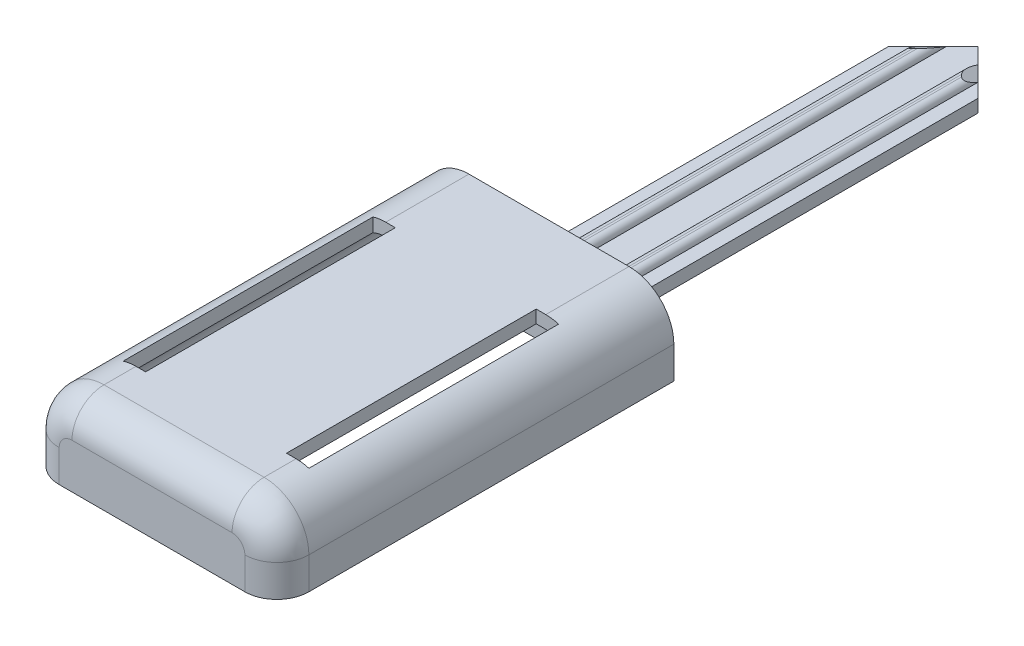
SolidWorks part; units mm, degrees
note: The reader was unsure of these and kept them because the rebuilt part matched: shared geometry of "Sketch2<2>".
ref_plane "Front" through (0, 0, 0) normal (0, 0, 1) x (1, 0, 0)
ref_plane "Top" through (0, 0, 0) normal (0, 1, 0) x (1, 0, 0)
ref_plane "Right" through (0, 0, 0) normal (1, 0, 0) x (0, 0, -1)
sketch "Sketch1" plane through (0, 0, 0) normal (0, 0, 1) x (1, 0, 0)
  line L0 (-12.5, 0) -> (12.5, 0)
  line L1 (-17.5, -5) -> (-17.5, -10)
  line L2 (17.5, -5) -> (17.5, -10)
  line L3 (-19.5, -5) -> (-19.5, -10)
  line L4 (-12.5, 2) -> (12.5, 2)
  line L5 (19.5, -5) -> (19.5, -10)
  line L6 (19.5, -10) -> (17.5, -10)
  line L7 (-17.5, -10) -> (-19.5, -10)
  line L8 (19.5, -10) -> (-49980.5, -10) construction
  arc A0 (12.5, 0) -> (17.5, -5) centre (12.5, -5) cw
  arc A1 (-12.5, 0) -> (-17.5, -5) centre (-12.5, -5) ccw
  arc A2 (-12.5, 2) -> (-19.5, -5) centre (-12.5, -5) ccw
  arc A3 (12.5, 2) -> (19.5, -5) centre (12.5, -5) cw
  point P4 (0, 0)
  point P8 (17.5, 0)
  point P11 (-17.5, 0)
  dimension "D2" = 5
  dimension "D1" = 35
  dimension "D4" = 12
  dimension "D3" = 2
extrude "Boss-Extrude1" add sketch "Sketch1" along normal blind 60
sketch "Sketch2" plane through (0, 0, 0) normal (0, 0, 1) x (1, 0, 0)
  line L0 (19.5, -10) -> (19.5, -5) construction
  line L1 (12.5, 2) -> (-12.5, 2) construction
  line L2 (-19.5, -5) -> (-19.5, -10) construction
  line L3 (19.5, -10) -> (19.5, -5)
  line L4 (12.5, 2) -> (-12.5, 2)
  line L5 (-19.5, -5) -> (-19.5, -10)
  line L6 (-19.5, -10) -> (19.5, -10)
  arc A0 (19.5, -5) -> (12.5, 2) centre (12.5, -5) ccw construction
  arc A1 (-12.5, 2) -> (-19.5, -5) centre (-12.5, -5) ccw construction
  arc A2 (19.5, -5) -> (12.5, 2) centre (12.5, -5) ccw
  arc A3 (-12.5, 2) -> (-19.5, -5) centre (-12.5, -5) ccw
extrude "Boss-Extrude2" add sketch "Sketch2" along normal blind 2
extrude "Boss-Extrude3" add sketch "Sketch2<2>" along normal blind 2 from surface at 60 starting at face at (0, -4.2525, 60)
sketch "Sketch2<2>" plane through (0, 0, 0) normal (0, 0, 1) x (1, 0, 0) same geometry as "Sketch2"
fillet "Fillet1" radius 5 10 edges at (19.5, -7.5, 62) (17.4497, -0.0503, 62) (-19.5, -7.5, 62) (-17.4497, -0.0503, 62) (0, 2, 62) (-17.5, -7.5, 60) (17.5, -7.5, 60) (16.0355, -1.4645, 60) (0, 0, 60) (-16.0355, -1.4645, 60)
sketch "Sketch3" plane through (0, -10, 0) normal (0, -1, 0) x (1, 0, 0)
  line L0 (0, 0) -> (0, -50000) construction
  line L1 (-19.5, 0) -> (19.5, 0) construction
  line L2 (-7, 0) -> (-7, -60)
  line L3 (-7, -60) -> (0, -67)
  line L4 (-7, 0) -> (7, 0)
  line L5 (7, -60) -> (0, -67)
  line L6 (7, 0) -> (7, -60)
  point P4 (0, 0)
  point P11 (0, 0)
  dimension "D1" = 7
  dimension "D2" = 45
  dimension "D3" = 60
extrude "Boss-Extrude4" add sketch "Sketch3" against normal blind 2
fillet "Fillet2" radius 2 3 edges at (7, -9, 0) (-7, -9, 0) (0, -8, 0)
sketch "Sketch4" plane through (0, -10, 0) normal (0, -1, 0) x (1, 0, 0)
  line L0 (-17.5, 2) -> (17.5, 2) construction
  line L1 (17.5, 55) -> (17.5, 2) construction
  line L2 (-17.5, 55) -> (-17.5, 2) construction
  line L3 (-12.5, 60) -> (12.5, 60) construction
  line L4 (-17.5, 2) -> (17.5, 2)
  line L5 (17.5, 55) -> (17.5, 2)
  line L6 (-17.5, 55) -> (-17.5, 2)
  line L7 (-12.5, 60) -> (12.5, 60)
  line L8 (-16.5, 3) -> (16.5, 3)
  line L9 (16.5, 55) -> (16.5, 3)
  line L10 (-12.5, 59) -> (12.5, 59)
  line L11 (-16.5, 55) -> (-16.5, 3)
  arc A0 (17.5, 55) -> (12.5, 60) centre (12.5, 55) ccw construction
  arc A1 (-12.5, 60) -> (-17.5, 55) centre (-12.5, 55) ccw construction
  arc A2 (17.5, 55) -> (12.5, 60) centre (12.5, 55) ccw
  arc A3 (-12.5, 60) -> (-17.5, 55) centre (-12.5, 55) ccw
  arc A4 (16.5, 55) -> (12.5, 59) centre (12.5, 55) ccw
  arc A5 (-12.5, 59) -> (-16.5, 55) centre (-12.5, 55) ccw
  dimension "D1" = 1
extrude "Boss-Extrude5" add sketch "Sketch4" along normal blind 2 and the other way blind 1
chamfer "Chamfer3" distance 1 angle 45 6 edges at (17.5, -9, 28.5) (16.0355, -9, 58.5355) (0, -9, 60) (-16.0355, -9, 58.5355) (0, -9, 2) (-17.5, -9, 28.5)
sketch "Sketch5" plane through (0, -8, 0) normal (0, 1, 0) x (1, 0, 0)
  line L0 (0, 0) -> (0, 50000) construction
  line L1 (0, 0) -> (-50000, 0) construction
  line L2 (-7, 60) -> (0, 67) construction
  line L3 (-4.826, 0) -> (-2.4776, 0)
  line L4 (-4.826, 0) -> (-4.826, 62.174)
  line L6 (-2.4776, 0) -> (-2.4776, 64.5224)
  line L7 (-2.4776, 64.5224) -> (-4.826, 62.174)
  line L8 (4.826, 0) -> (4.826, 62.174)
  line L9 (2.4776, 64.5224) -> (4.826, 62.174)
  line L10 (2.4776, 0) -> (2.4776, 64.5224)
  line L11 (4.826, 0) -> (2.4776, 0)
extrude "Boss-Extrude6" add sketch "Sketch5" along normal blind 1
fillet "Fillet3" radius 1 4 edges at (4.826, -7, -31.221) (2.4776, -7, -32.3952) (-2.4776, -7, -32.3952) (-4.826, -7, -31.221)
chamfer "Chamfer4" distance 1 angle 61 2 edges at (-3.6518, -7, -63.3482) (3.6518, -7, -63.3482)
sketch "Sketch6" plane through (0, 2, 0) normal (0, 1, 0) x (1, 0, 0)
  line L0 (12.75, -57) -> (12.75, 49943) construction
  line L1 (14.5, -52) -> (11, -52)
  line L2 (14.5, -52) -> (14.5, -13)
  line L3 (14.5, -13) -> (11, -13)
  line L4 (11, -52) -> (11, -13)
  line L5 (0, -57) -> (0, 49943) construction
  line L6 (-12.5, -57) -> (12.5, -57) construction
  line L7 (12.5, 0) -> (-12.5, 0) construction
  line L8 (-14.5, -13) -> (-11, -13)
  line L9 (-11, -52) -> (-11, -13)
  line L10 (-14.5, -52) -> (-11, -52)
  line L11 (-14.5, -52) -> (-14.5, -13)
  line L13 (19.5, -57) -> (19.5, 0) construction
  point P8 (12.75, -52)
  point P13 (0, -57)
  point P16 (0, 0)
  dimension "D1" = 3.5
  dimension "D2" = 39
  dimension "D3" = 13
  dimension "D4" = 6.75
extrude "Cut-Extrude1" cut sketch "Sketch6" against normal through all both and the other way through all
